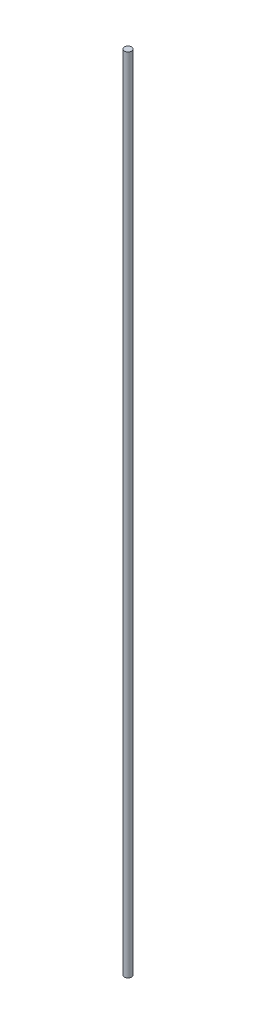
SolidWorks part; units mm, degrees
ref_plane "Спереди" through (0, 0, 0) normal (0, 0, 1) x (1, 0, 0)
ref_plane "Сверху" through (0, 0, 0) normal (0, 1, 0) x (1, 0, 0)
ref_plane "Справа" through (0, 0, 0) normal (1, 0, 0) x (0, 0, -1)
sketch "Эскиз2" plane through (0, 0, 0) normal (0, 0, 1) x (1, 0, 0)
  line L5 (-2.5, 275) -> (0, 275)
  line L6 (-2.5, 275) -> (-2.5, -275)
  line L7 (-2.5, -275) -> (0, -275)
  line L8 (0, 275) -> (0, -275)
  line L9 (-2.5, 275) -> (0, -275) construction
  line L10 (-2.5, -275) -> (0, 275) construction
  point P0 (-1.25, 0)
  point P5 (0, 0)
  dimension "D1" = 2.5
  dimension "D2" = 550
revolve "Повернуть1" add sketch "Эскиз2" angle 360 about L6
equation "\"Ширина груза\"= 420"
equation "\"Глубина груза\"= 490"
equation "\"Высота груза\"= 297"
equation "\"Ширина ячейки\"= \"Ширина груза\" + 10"
equation "\"Глубина ячейки\"= \"Глубина груза\" + 10"
equation "\"Высота ячейки\"= \"Высота груза\" + 10 + 13"
equation "\"Колво ячеек ширина\"= 2"
equation "\"Колво ячеек высота\"= 2"
equation "\"Толщина стенки\"= 10"
equation "\"Крепление дверцы\"= 5"
equation "\"Ширина рейки\"= \"Толщина шестерни\""
equation "\"Высота рейки\"= 20"
equation "\"Высота пола\"= 20"
equation "\"Колво полозьев\"= 5"
equation "\"Отступ рейки\"= 20"
equation "\"Глубина каретки\"= \"Глубина ячейки\" + 30 + \"Мотор Y высота корпуса\" + 20"
equation "\"Длинна рейки\"= ( \"Ширина ячейки\" + \"Толщина стенки\" + \"Крепление дверцы\" ) * \"Колво ячеек ширина\" + \"Ширина ячейки выгрузки\" * \"Колво выгрузки\" + \"Толщина стенки\""
equation "\"Отступ шпильки\"= 20"
equation "\"Диаметр шпильки\"= 5"
equation "\"Длинна шпильки\"= ( \"Высота ячейки\" + \"Толщина стенки\" + \"Высота пола\" ) * \"Колво ячеек высота\" + ( \"Толщина стенки\" + \"Отступ рейки\" ) * 2 "
equation "\"D1@Эскиз2\"= \"Диаметр шпильки\" / 2"
equation "\"D2@Эскиз2\"= \"Глубина каретки\" - \"Мотор Y высота корпуса\""
equation "\"Ширина пластины\"= 50  "
equation "\"Высота зона выгрузки\"= \"Высота ячейки\" * 2 + \"Толщина стенки\" * 2"
equation "\"Колво выгрузки\"= 1"
equation "\"Отступ крепления мотора фиксации\" = 30"
equation "\"Мотор X ширина корпуса\"= 42.3"
equation "\"Мотор X высота корпуса\"= 42.3"
equation "\"Мотор X длина корпуса\"= 40"
equation "\"Мотор X вылет вала\"= 19.8"
equation "\"Мотор Y ширина корпуса\"= 42.3"
equation "\"Мотор Y высота корпуса\"= 42.3"
equation "\"Мотор Y длина корпуса\"= 48"
equation "\"Мотор Y вылет вала\"= 30"
equation "\"Мотор Z ширина корпуса\"= 42"
equation "\"Мотор Z высота корпуса\"= 42"
equation "\"Мотор Z длина корпуса\"= 40"
equation "\"Мотор Z вылет вала\"= 23"
equation "\"Мотор диаметр вала ПРЕДВ\"= 5"
equation "\"Мотор шаг крепления ПРЕДВ\"= 31"
equation "\"Мотор диаметр отверстий ПРЕДВ\"= 3"
equation "\"Мотор глубина отверстий ПРЕДВ\"= 4.5"
equation "\"Мотор диаметр буртика ПРЕДВ\"= 22"
equation "\"Мотор высота буртика ПРЕДВ\"= 2"
equation "\"Мотор диаметр шкива ПРЕДВ\"= 16"
equation "\"Мотор длина шкива ПРЕДВ\"= 12"
equation "\"Мотор отступ шкива ПРЕДВ\"= 5"
equation "\"Мотор X шаг градусов\"= 1.8"
equation "\"Мотор X ток А\"= 1.5"
equation "\"Мотор X сопротивление Ом\"= 1.3"
equation "\"Мотор X индуктивность мГн\"= 2"
equation "\"Мотор Y шаг градусов\"= 1.8"
equation "\"Мотор Y ток А\"= 2.2"
equation "\"Мотор Y сопротивление Ом\"= 0.9"
equation "\"Мотор Y индуктивность мГн\"= 2"
equation "\"Мотор Z шаг градусов\"= 1.8"
equation "\"Мотор Z ток А\"= 1"
equation "\"Мотор Z сопротивление Ом\"= 4"
equation "\"Мотор Z индуктивность мГн\"= 8"
equation "\"Мотор Y диаметр ротора\"= 25.78"
equation "\"Ширина ячейки выгрузки\"= \"Ширина ячейки\" + \"Толщина стенки\" + \"Отступ крепления мотора фиксации\"*2"
